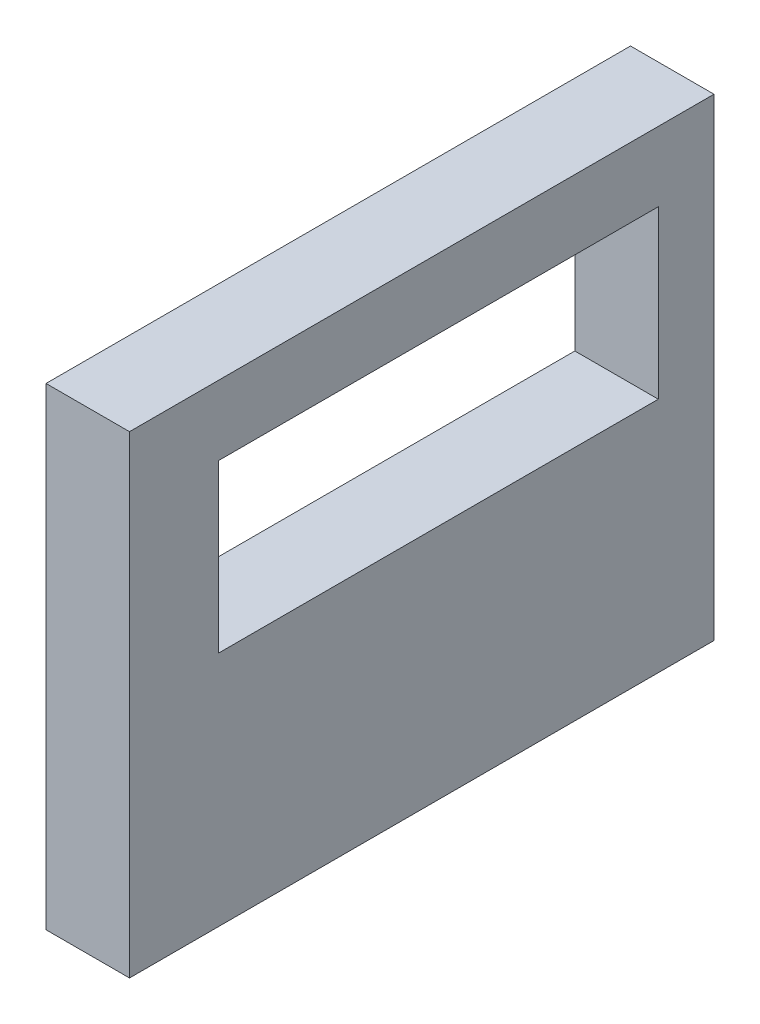
SolidWorks part; units mm, degrees
material "Polyurethane Foam Rigid"
ref_plane "X-Y Datum" through (0, 0, 0) normal (0, 0, 1) x (1, 0, 0)
ref_plane "X-Z Datum" through (0, 0, 0) normal (0, 1, 0) x (1, 0, 0)
ref_plane "Y-Z Datum" through (0, 0, 0) normal (1, 0, 0) x (0, 0, -1)
sketch "Sketch4" plane through (0, 0, 0) normal (0, 0, 1) x (1, 0, 0)
  line L1 (-19.05, -120.65) -> (19.05, -120.65)
  line L2 (-19.05, -120.65) -> (-19.05, 120.65)
  line L3 (-19.05, 120.65) -> (19.05, 120.65)
  line L4 (19.05, -120.65) -> (19.05, 120.65)
  line L5 (-19.05, -120.65) -> (19.05, 120.65) construction
  line L6 (-19.05, 120.65) -> (19.05, -120.65) construction
  point P0 (0, 0)
  dimension "D1" = 38.1
  dimension "D2" = 241.3
extrude "Boss-Extrude1" add sketch "Sketch4" along normal blind 266.7
sketch "Sketch11" plane through (19.05, 0, 0) normal (1, 0, 0) x (0, 0, -1)
  line L0 (-25.4, 88.9) -> (-25.4, 12.825) construction
  line L1 (-226, 88.9) -> (-25.4, 88.9) construction
  line L2 (-25.4, 12.825) -> (-226, 12.825) construction
  line L3 (-226, 88.9) -> (-226, 12.825) construction
  line L4 (-25.4, 88.9) -> (-25.4, 12.825)
  line L5 (-226, 88.9) -> (-25.4, 88.9)
  line L6 (-25.4, 12.825) -> (-226, 12.825)
  line L7 (-226, 88.9) -> (-226, 12.825)
extrude "Cut-Extrude3" cut sketch "Sketch11" against normal through all contours L5 L7 L6 L4 region at (19.05, 50.8625, 125.7)
sketch "Sketch13" plane through (0, -120.65, 0) normal (0, -1, 0) x (1, 0, 0)
  line L1 (19.05, 266.7) -> (-19.05, 266.7)
  line L2 (19.05, 266.7) -> (19.05, 0)
  line L3 (19.05, 0) -> (-19.05, 0)
  line L4 (-19.05, 266.7) -> (-19.05, 0)
  line L5 (19.05, 266.7) -> (-19.05, 0) construction
  line L6 (19.05, 0) -> (-19.05, 266.7) construction
  point P4 (0, 133.35)
  dimension "D1" = 38.1
  dimension "D2" = 266.7
extrude "Cut-Extrude5" cut sketch "Sketch13" against normal blind 25.4
